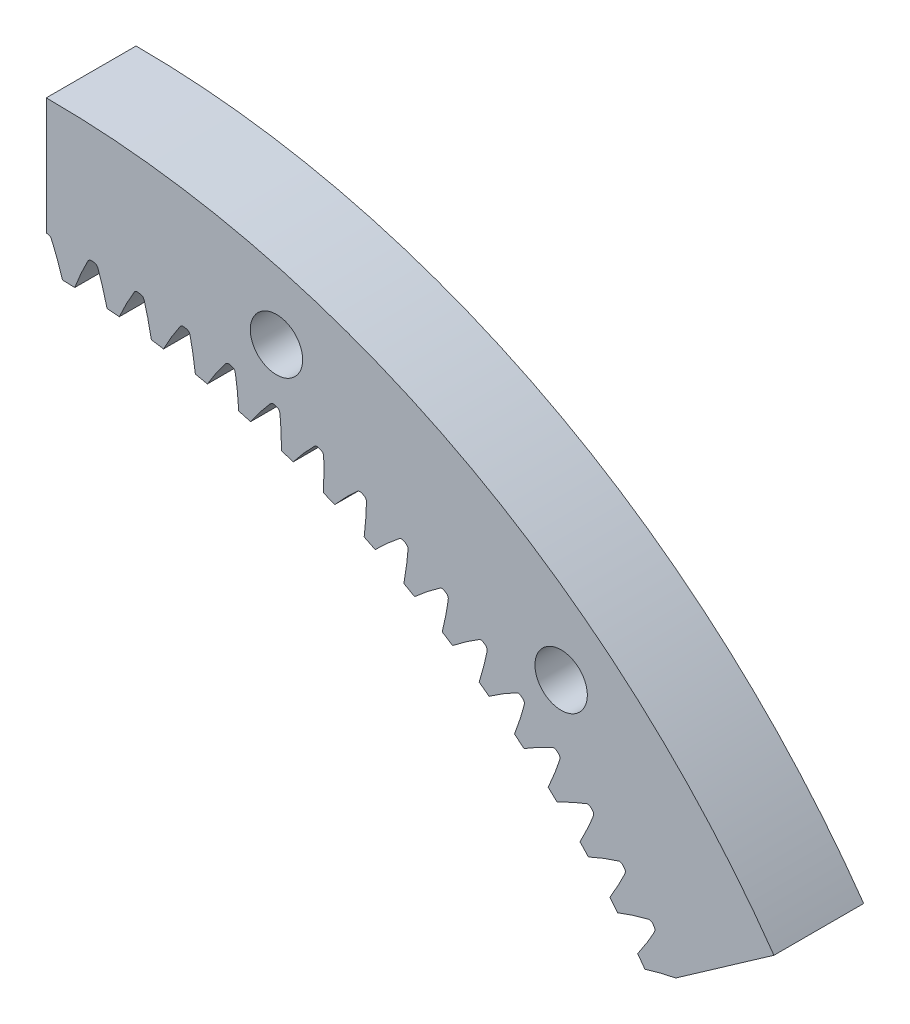
SolidWorks part; units mm, degrees
material "Д16 ГОСТ 4784-97"
ref_plane "FRONT" through (0, 0, 0) normal (0, 0, 1) x (1, 0, 0)
ref_plane "TOP" through (0, 0, 0) normal (0, 1, 0) x (1, 0, 0)
ref_plane "RIGHT" through (0, 0, 0) normal (1, 0, 0) x (0, 0, -1)
ref_axis "Ось1" through (0, 0, 50) along (0, 0, -1)
sketch "SketchRevolveSpurAssemblyNew2Gear" plane through (0, 0, 0) normal (1, 0, 0) x (0, 0, -1)
  line L0 (0, 0) -> (1, 0) construction
  line L1 (-2, 49.399) -> (-2, 59.399)
  line L2 (-2, 59.399) -> (4, 59.399)
  line L3 (4, 59.399) -> (4, 49.399)
  line L4 (4, 49.399) -> (-2, 49.399)
  dimension "MinorDiameter" = 49.399
  dimension "D1" = 6
  dimension "D2" = 10
revolve "SpurAssemblyNew2Gear" add sketch "SketchRevolveSpurAssemblyNew2Gear" angle 360 about L0
sketch "SketchToothSpurAssemblyNew2Gear" plane through (0, 0, 0) normal (0, 0, 1) x (1, 0, 0)
  arc A0 (49.1395, -1.1537) -> (49.1395, 1.1537) centre (0, 0) ccw
  spline S0 degree 3 poles (49.1395, 1.1537) (49.2861, 1.1124) (49.5102, 1.0454) (49.8138, 0.9473) (50.0554, 0.8652) (50.306, 0.7758) (50.5651, 0.6788) (50.8329, 0.5746) (51.108, 0.4599) (51.3094, 0.3804) (51.4272, 0.3224) (51.4611, 0.2973) (51.4911, 0.268) (51.5164, 0.2347) (51.5367, 0.198) (51.5565, 0.1461) (51.5633, 0.0916) (51.5623, 0.0385) (51.5626, 0) (51.5623, -0.0385) (51.5633, -0.0916) (51.5565, -0.1461) (51.5367, -0.198) (51.5164, -0.2347) (51.4911, -0.268) (51.4611, -0.2973) (51.4272, -0.3224) (51.3094, -0.3804) (51.108, -0.4599) (50.8329, -0.5746) (50.5651, -0.6788) (50.306, -0.7758) (50.0554, -0.8652) (49.8138, -0.9473) (49.5102, -1.0454) (49.2861, -1.1124) (49.1395, -1.1537) knots 0 0 0 0 0.081489 0.125094 0.170606 0.218025 0.26735 0.318583 0.371722 0.426768 0.434365 0.441808 0.449251 0.456695 0.464138 0.471581 0.486277 0.493139 0.5 0.506861 0.513723 0.528419 0.535862 0.543305 0.550749 0.558192 0.565635 0.573232 0.628278 0.681417 0.73265 0.781975 0.829394 0.874906 0.918511 1 1 1 1
extrude "ToothExtrudeCutSpurAssemblyNew2Gear" cut sketch "SketchToothSpurAssemblyNew2Gear" against normal blind 4 and the other way blind 4
pattern_circular "PatternSpurAssemblyNew2Gear" count 104 every 3.462 about axis through (0, 0, 50) along (0, 0, -1) of "ToothExtrudeCutSpurAssemblyNew2Gear"
sketch "AuxiliarySketchSpurAssemblyNew2Gear" plane through (0, 0, 0) normal (0, 0, 1) x (1, 0, 0)
  circle A0 centre (0, 0) radius 50 construction
  circle A1 centre (0, 0) radius 46.9846 construction
  circle A2 centre (0, 0) radius 51.5625 construction
  circle A3 centre (0, 0) radius 49.399 construction
  dimension "PitchDiameter" = 100
  dimension "BaseDiameter" = 93.9693
  dimension "MajorDiameter" = 103.125
  dimension "MinorDiameter" = 98.7981
sketch "Эскиз1" plane through (0, 0, 2) normal (0, 0, 1) x (1, 0, 0)
  line L0 (0, 0) -> (0, 72.3035)
  line L1 (0, 0) -> (59.2276, 41.4716)
  line L2 (0, 0) -> (25.3962, 48.7856) construction
  line L3 (0, 0) -> (15.3906, 52.8027) construction
  line L4 (34.4258, 42.8936) -> (0, 0) construction
  arc A0 (0, 72.3035) -> (59.2276, 41.4716) centre (0, 0) ccw
  arc A1 (45.0534, 31.5467) -> (0, 55) centre (0, 0) ccw construction
  circle A2 centre (15.3906, 52.8027) radius 1.75
  circle A4 centre (34.4258, 42.8936) radius 1.75
  dimension "D2" = 11.25
  dimension "D3" = 72.3035
  dimension "D4" = 3.5
  dimension "D5" = 110
  dimension "D1" = 55
extrude "Вырез-Вытянуть1" cut sketch "Эскиз1" against normal through all
